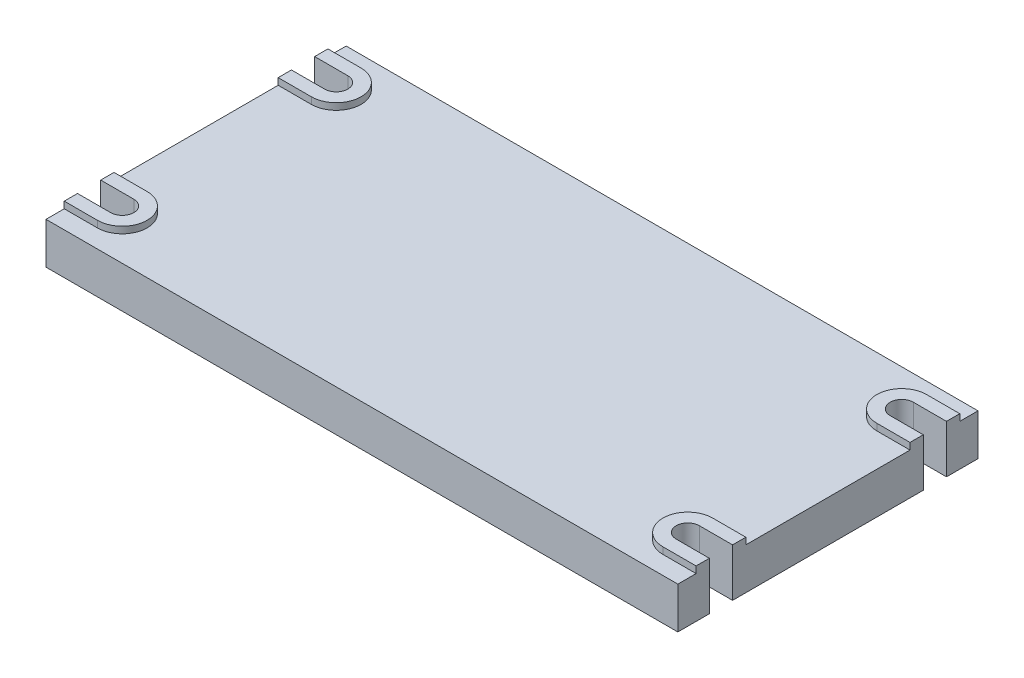
SolidWorks part; units mm, degrees
ref_plane "前视基准面" through (0, 0, 0) normal (0, 0, 1) x (1, 0, 0)
ref_plane "上视基准面" through (0, 0, 0) normal (0, 1, 0) x (1, 0, 0)
ref_plane "右视基准面" through (0, 0, 0) normal (1, 0, 0) x (0, 0, -1)
sketch "草图1" plane through (0, 0, 0) normal (0, 1, 0) x (1, 0, 0)
  line L1 (-190.5, -90.5) -> (190.5, -90.5)
  line L2 (-190.5, -90.5) -> (-190.5, 90.5)
  line L3 (-190.5, 90.5) -> (190.5, 90.5)
  line L4 (190.5, -90.5) -> (190.5, 90.5)
  line L5 (-190.5, -90.5) -> (190.5, 90.5) construction
  line L6 (-190.5, 90.5) -> (190.5, -90.5) construction
  point P0 (0, 0)
  dimension "D1" = 381
  dimension "D2" = 181
extrude "凸台-拉伸1" add sketch "草图1" along normal blind 25
sketch "草图2" plane through (0, 25, 0) normal (0, 1, 0) x (1, 0, 0)
  line L0 (-208.3022, 64.5) -> (-190.5, 64.5) construction
  line L1 (190.5, 90.5) -> (-190.5, 90.5) construction
  line L2 (-190.5, 90.5) -> (-190.5, -90.5) construction
  line L3 (-170.5, 57.5) -> (-190.5, 57.5)
  line L4 (-170.5, 79.5) -> (-190.5, 79.5)
  line L5 (-170.5, 71.5) -> (-190.5, 71.5)
  line L6 (-190.5, 57.5) -> (-190.5, 71.5)
  line L7 (-190.5, 49.5) -> (-170.5, 49.5)
  line L9 (-163.5, 64.5) -> (-122.6811, 64.5) construction
  line L10 (-170.5, 79.5) -> (-198.5, 79.5) construction
  line L11 (-198.5, 49.5) -> (-198.5, 79.5) construction
  line L12 (-170.5, 49.5) -> (-198.5, 49.5) construction
  arc A0 (-170.5, 49.5) -> (-170.5, 79.5) centre (-170.5, 64.5) ccw
  arc A1 (-170.5, 57.5) -> (-170.5, 71.5) centre (-170.5, 64.5) ccw
  point P4 (-180.5, 64.5)
  line M3 (-190.5, 90.5) -> (-190.5, -90.5)
  dimension "D1" = 26
  dimension "D2" = 20
  dimension "D3" = 14
  dimension "D4" = 8
extrude "切除-拉伸1" cut sketch "草图2" against normal blind 25 contours L3 A1 L5 M3 region at (-177.7032, 25, -64.5)
extrude "凸台-拉伸2" add sketch "草图2<3>" along normal blind 4 contours A1 L3 L7 A0 L4 L5 M3 region at (-163.039, 25, -64.5)
sketch "草图2<3>" plane through (0, 25, 0) normal (0, 1, 0) x (1, 0, 0) same geometry as "草图2"
mirror "镜向1" about plane through (0, 0, 0) normal (0, 0, 1) of "切除-拉伸1", "凸台-拉伸2"
mirror "镜向2" about plane through (0, 0, 0) normal (1, 0, 0) of "镜向1"
